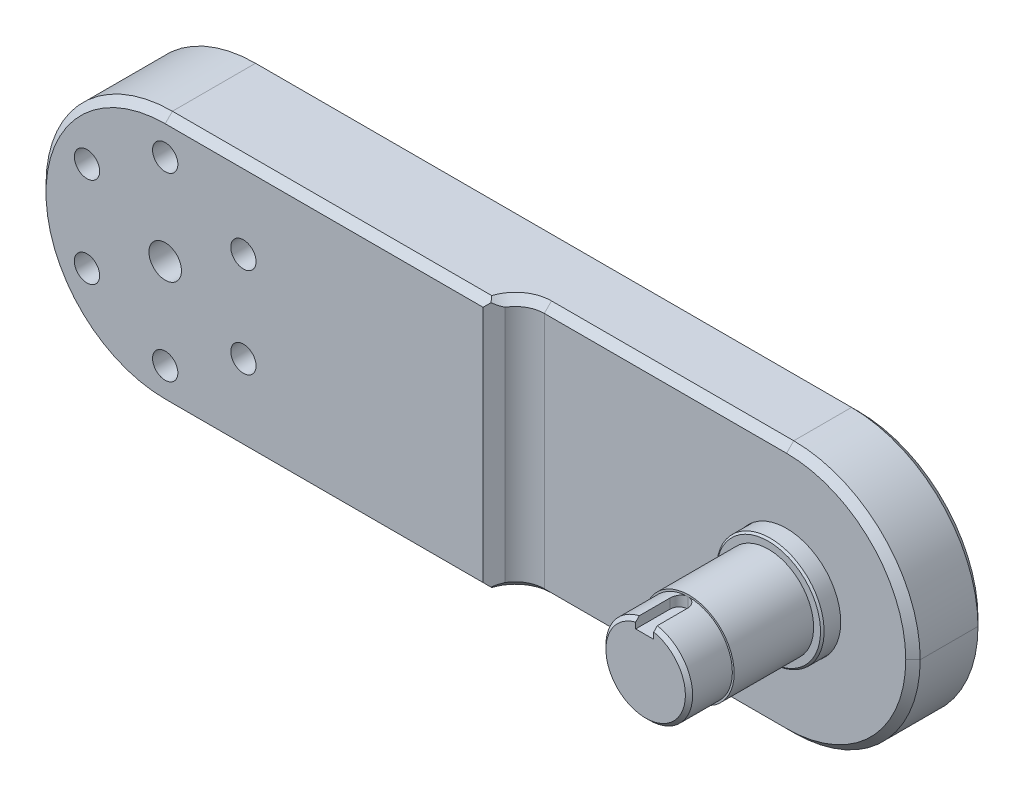
SolidWorks part; units mm, degrees
ref_plane "前视基准面" through (0, 0, 0) normal (0, 0, 1) x (1, 0, 0)
ref_plane "上视基准面" through (0, 0, 0) normal (0, 1, 0) x (1, 0, 0)
ref_plane "右视基准面" through (0, 0, 0) normal (1, 0, 0) x (0, 0, -1)
sketch "草图1" plane through (0, 0, 0) normal (0, 0, 1) x (1, 0, 0)
  circle A0 centre (0, 0) radius 35
  dimension "D1" = 70
extrude "拉伸1" add sketch "草图1" along normal blind 27
sketch "草图2" plane through (0, 0, 0) normal (0, 0, -1) x (-1, 0, 0)
  circle A0 centre (0, 0) radius 30
extrude "切除-拉伸1" cut sketch "草图2" against normal blind 13
sketch "草图3" plane through (0, 0, 13) normal (0, 0, -1) x (-1, 0, 0)
  circle A1 centre (0, 25) radius 3.5
  circle A2 centre (21.6506, 12.5) radius 3.5
  circle A3 centre (21.6506, -12.5) radius 3.5
  circle A4 centre (0, -25) radius 3.5
  circle A5 centre (-21.6506, -12.5) radius 3.5
  circle A6 centre (-21.6506, 12.5) radius 3.5
extrude "切除-拉伸2" cut sketch "草图3" against normal blind 18
sketch "草图5" plane through (0, 0, 27) normal (0, 0, 1) x (1, 0, 0)
  line L0 (0, 35) -> (150, 35)
  line L1 (0, -35) -> (150, -35)
  line L3 (150, 35) -> (200, 35)
  line L5 (150, -35) -> (200, -35)
  line L6 (200, 35) -> (200, -35)
  circle A0 centre (0, 0) radius 35 construction
  arc A1 (0, -35) -> (0, 35) centre (0, 0) ccw
  dimension "D1" = 200
extrude "拉伸3" add sketch "草图5" against normal blind 27
sketch "草图6" plane through (0, 0, 27) normal (0, 0, 1) x (1, 0, 0)
  circle A0 centre (0, 0) radius 4.5
extrude "切除-拉伸3" cut sketch "草图6" against normal blind 25
fillet "圆角2" radius 35 2 edges at (200, -35, 13.5) (200, 35, 13.5)
sketch "草图13" plane through (0, 0, 27) normal (0, 0, 1) x (1, 0, 0)
  line L1 (250, 52.0228) -> (90, 52.0228)
  line L2 (250, 52.0228) -> (250, -52.963)
  line L3 (250, -52.963) -> (90, -52.963)
  line L4 (90, 52.0228) -> (90, -52.963)
  arc A0 (0, 35) -> (0, -35) centre (0, 0) ccw construction
  dimension "D1" = 90
extrude "切除-拉伸7" cut sketch "草图13" against normal blind 7
fillet "圆角4" radius 8 1 edges at (90, 0, 20)
chamfer "倒角1" distance 2 angle 45 5 edges at (189.7487, -24.7487, 0) (82.5, -35, 0) (189.7487, 24.7487, 0) (-35, 0, 0) (82.5, 35, 0)
chamfer "倒角2" distance 2 angle 45 9 edges at (92.6458, -35, 22) (131.4686, -35, 20) (189.7487, -24.7487, 20) (189.7487, 24.7487, 20) (92.6458, 35, 22) (131.4686, 35, 20) (45, -35, 27) (-35, 0, 27) (45, 35, 27)
chamfer "倒角3" distance 2 angle 45 1 edges at (90, 0, 27) first distance on face at (36.75, 0, 27)
sketch "草图14" plane through (0, 0, 20) normal (0, 0, 1) x (1, 0, 0)
  circle A0 centre (165, 0) radius 15
extrude "切除-拉伸8" cut sketch "草图14" against normal blind 53
ref_plane "基准面1" through (0, 0, 3) normal (0, 0, -1) x (-1, 0, 0)
sketch "草图15" plane through (0, 0, 3) normal (0, 0, -1) x (-1, 0, 0)
  circle A0 centre (-165, 0) radius 14.9
extrude "拉伸5" add sketch "草图15" against normal blind 22
sketch "草图17" plane through (0, 0, 25) normal (0, 0, 1) x (1, 0, 0)
  circle A0 centre (165, 0) radius 12.5
extrude "拉伸6" add sketch "草图17" along normal blind 34
sketch "草图18" plane through (0, 0, 59) normal (0, 0, 1) x (1, 0, 0)
  circle A0 centre (165, 0) radius 12.5
  circle A1 centre (165, 0) radius 12
extrude "切除-拉伸9" cut sketch "草图18" against normal blind 12
chamfer "倒角6" distance 1 angle 45 1 edges at (177, 0, 59)
chamfer "倒角7" distance 0.5 angle 45 1 edges at (150.1, 0, 25)
sketch "草图19" plane through (0, 0, 0) normal (0, 0, -1) x (-1, 0, 0)
  circle A0 centre (-165, 0) radius 17.5
  circle A1 centre (-165, 0) radius 15
  dimension "D1" = 35
extrude "切除-拉伸10" cut sketch "草图19" against normal blind 3
sketch "草图20" plane through (0, 0, 3) normal (0, 0, -1) x (-1, 0, 0)
  circle A1 centre (-165, 0) radius 17.45
  dimension "D1" = 34.9
extrude "拉伸7" add sketch "草图20" along normal blind 3
sketch "草图21" plane through (0, 0, 59) normal (0, 0, 1) x (1, 0, 0)
  line L1 (162.2397, 12) -> (167.2397, 12)
  line L2 (162.2397, 12) -> (162.2397, 9)
  line L3 (162.2397, 9) -> (167.2397, 9)
  line L4 (167.2397, 12) -> (167.2397, 9)
  dimension "D2" = 3
extrude "切除-拉伸11" cut sketch "草图21" against normal blind 12
fillet "圆角5" radius 2.5 2 edges at (167.2397, 10.3946, 47) (162.2397, 10.3391, 47)
